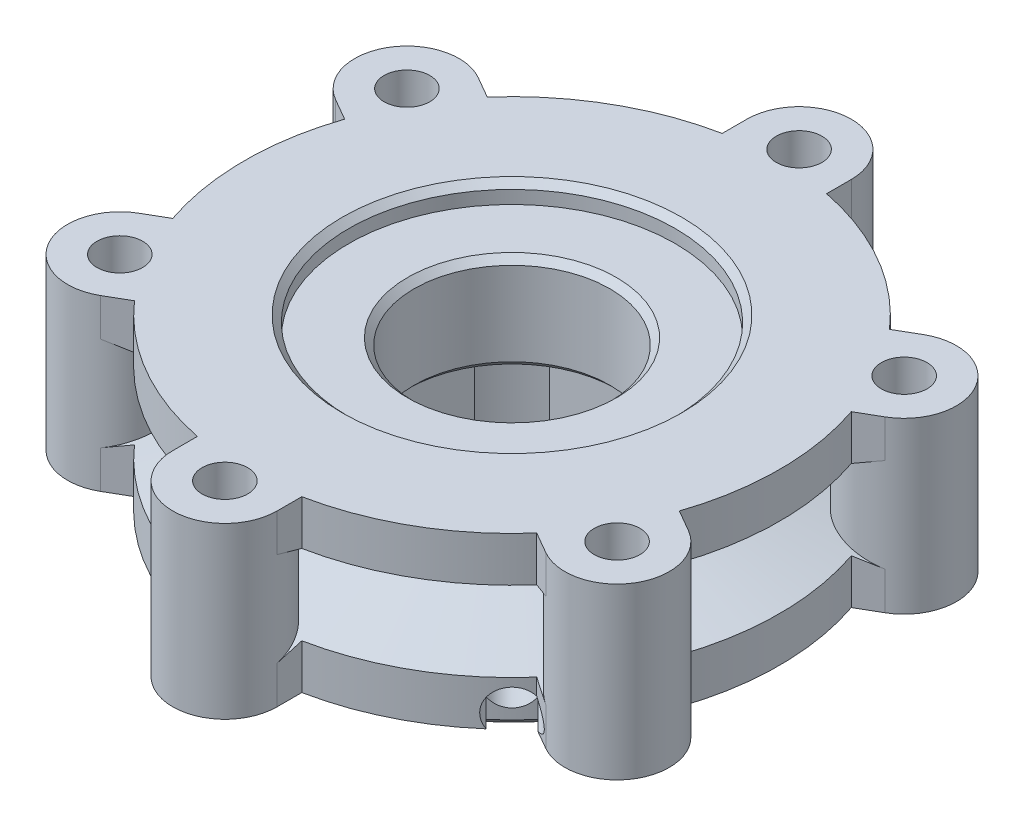
SolidWorks part; units mm, degrees
material "PLA/ABS"
ref_plane "Front Plane" through (0, 0, 0) normal (0, 0, 1) x (1, 0, 0)
ref_plane "Top Plane" through (0, 0, 0) normal (0, 1, 0) x (1, 0, 0)
ref_plane "Right Plane" through (0, 0, 0) normal (1, 0, 0) x (0, 0, -1)
other "Bounding Box"
ref_plane "Default Plane" through (13.8565, 3.175, 6.7999) normal (0, -1, 0) x (-1, 0, 0)
sketch "Sketch1" plane through (0, 0, 0) normal (0, 1, 0) x (1, 0, 0)
  line L0 (26.9408, -26.9408) -> (0, 0) construction
  line L1 (0, 0) -> (26.9408, 26.9408) construction
  line L2 (0, 0) -> (0, 38.1) construction
  circle A0 centre (0, 0) radius 38.1
  point P3 (0, 38.1)
  point P4 (38.1, 0)
  point P5 (-38.1, 0)
  point P6 (0, -38.1)
  point P7 (26.9408, 26.9408)
  point P8 (26.9408, -26.9408)
  dimension "D1" = 76.2
  dimension "D2" = 45
extrude "Boss-Extrude1" add sketch "Sketch1" along normal mid plane 16.51
ref_plane "Plane2" through (-38.1, 0, 0) normal (-1, 0, 0) x (0, 0, 1)
sketch "Sketch9" plane through (-38.1, 0, 0) normal (-1, 0, 0) x (0, 0, 1)
  line L0 (-0.635, -8.255) -> (0.635, -8.255)
  line L1 (-38.1, -8.255) -> (38.1, -8.255) construction
  line L2 (0.635, -8.255) -> (0.635, 0)
  line L3 (38.1, 8.255) -> (-38.1, 8.255) construction
  line L5 (-0.635, 0) -> (-0.635, -8.255)
  line L6 (0.635, -8.255) -> (0, -8.255) construction
  line L7 (0, -8.255) -> (0, 8.255) construction
  line L9 (-0.635, 0) -> (0.635, 0) construction
  line L10 (0.635, 0) -> (0.635, 8.255)
  line L11 (0.635, 8.255) -> (-0.635, 8.255)
  line L13 (-0.635, 8.255) -> (-0.635, 0)
  point P14 (0, 0)
  dimension "D2" = 1.27
extrude "Cut-Extrude4" cut sketch "Sketch9" against normal blind 0.635
sketch "Sketch4" plane through (0, 0, 0) normal (0, 0, 1) x (1, 0, 0)
  line L0 (-38.1, -8.255) -> (-35.56, -8.255)
  line L1 (-38.0947, -8.255) -> (38.1, -8.255) construction
  line L4 (38.1, 8.255) -> (-38.0947, 8.255) construction
  line L5 (-35.56, 8.255) -> (-38.1, 8.255)
  line L6 (-38.1, 8.255) -> (-38.1, -8.255)
  line L7 (-12.7, 0) -> (0, 0) construction
  line L8 (-35.56, -8.255) -> (-35.56, -6.6675)
  line L9 (-35.56, -6.6675) -> (-12.7, 0)
  line L10 (-12.7, 0) -> (-35.56, 6.6675)
  line L11 (-35.56, 6.6675) -> (-35.56, 8.255)
  point P17 (-38.1, 0)
  dimension "D1" = 2.54
  dimension "D2" = 25.4
  dimension "D3" = 1.5875
pattern_circular "CirPattern2" count 25 over 360 about axis through (0, -8.255, 0) along (0, 1, 0) of "Cut-Extrude4"
ref_axis "Axis1" through (0, -8.7312, 0) along (0, 1, 0)
sketch "Sketch3" plane through (0, 8.255, 0) normal (0, 1, 0) x (1, 0, 0)
  line L0 (0, 0) -> (0, 27.94) construction
  line L1 (0, 27.94) -> (0, 38.1) construction
  circle A0 centre (0, 27.94) radius 2.2225
  circle A1 centre (0, 0) radius 38.1 construction
  circle A2 centre (0, 27.94) radius 5.08
  dimension "D2" = 4.445
  dimension "D3" = 10.16
  dimension "D1" = 10.16
move or copy body "Body-Move/Copy1" [suppressed]
revolve "Cut-Revolve2" cut sketch "Sketch4" angle 360 about axis through (0, -8.7312, 0) along (0, 1, 0)
sketch "Sketch5" plane through (0, 8.255, 0) normal (0, 1, 0) x (1, 0, 0)
  circle A0 centre (0, 27.94) radius 5.08
  circle A1 centre (0, 27.94) radius 2.2225 construction
  circle A3 centre (0, 27.94) radius 2.2225
  circle A4 centre (0, 27.94) radius 5.08 construction
extrude "Boss-Extrude2" add sketch "Sketch5" against normal through all
sketch "Sketch12" plane through (0, 8.255, 0) normal (0, 1, 0) x (1, 0, 0)
  line L0 (-24.1967, 13.97) -> (0, 0) construction
  line L1 (-24.1967, -13.97) -> (-24.1967, 13.97) construction
  line L2 (-24.1967, 13.97) -> (0, 27.94) construction
  line L3 (-24.1967, -13.97) -> (0, 0) construction
  line L4 (0, 0) -> (0, 27.94) construction
  circle A0 centre (-24.1967, 13.97) radius 5.08
  circle A1 centre (0, 27.94) radius 5.08 construction
  dimension "D3" = 120
extrude "Boss-Extrude6" add sketch "Sketch12" against normal through all
sketch "Sketch17" plane through (0, 0, 0) normal (0, 1, 0) x (1, 0, 0)
  line L0 (0, 27.94) -> (0, 0) construction
  line L1 (0, 0) -> (-24.1967, 13.97) construction
  line L2 (0, 0) -> (-24.1967, -13.97) construction
  line L3 (-28.5962, -16.51) -> (-30.7959, -17.78)
  line L4 (0, 33.02) -> (0, 35.56)
  line L5 (-26.7367, -9.5706) -> (-24.6536, -8.3679)
  line L6 (-24.6536, 8.3679) -> (-26.7367, 9.5706)
  line L7 (-21.6567, 18.3694) -> (-19.5736, 17.1667)
  line L8 (-5.08, 27.94) -> (-5.08, 25.5346)
  circle A0 centre (0, 27.94) radius 5.08 construction
  circle A1 centre (-24.1967, 13.97) radius 5.08 construction
  arc A2 (0, 33.02) -> (-5.08, 27.94) centre (0, 27.94) ccw
  arc A3 (-21.6567, 18.3694) -> (-26.7367, 9.5706) centre (-24.1967, 13.97) ccw
  arc A5 (-5.08, 25.5346) -> (-19.5736, 17.1667) centre (0, 0) ccw
  circle A6 centre (0, 27.94) radius 2.2225 construction
  arc A7 (-26.7367, -9.5706) -> (-28.5962, -16.51) centre (-24.1967, -13.97) ccw
  circle A8 centre (0, 0) radius 35.56 construction
  circle A9 centre (0, 27.94) radius 2.2225
  circle A10 centre (0, 0) radius 35.56 construction
  arc A11 (0, 35.56) -> (-30.7959, -17.78) centre (0, 0) ccw
  arc A12 (-24.6536, 8.3679) -> (-24.6536, -8.3679) centre (0, 0) ccw
  circle A13 centre (-24.1967, 13.97) radius 2.2225
  circle A15 centre (-24.1967, -13.97) radius 2.2225
  dimension "D1" = 9.525
extrude "Cut-Extrude5" cut sketch "Sketch17" against normal through all both and the other way through all
pattern_circular "CirPattern1" count 3 over 360 about axis through (0, 6.6675, 0) along (0, -1, 0) of "Boss-Extrude2", "Boss-Extrude6", "Cut-Extrude5"
sketch "Sketch18" plane through (0, -8.255, 0) normal (0, -1, 0) x (1, 0, 0)
  circle A0 centre (0, 0) radius 26.035 construction
  circle A1 centre (0, 0) radius 16.51
  arc A2 (-5.08, 25.5346) -> (-19.5736, 17.1667) centre (0, 0) ccw construction
  circle A3 centre (0, 0) radius 12.7 construction
  circle A4 centre (0, 0) radius 12.7 construction
  dimension "D1" = 3.81
extrude "Boss-Extrude9" add sketch "Sketch18" against normal through all
fillet "Fillet5" radius 1.27 2 edges at (0, -1.1112, -16.51) (0, 1.1112, 16.51)
sketch "Sketch22" plane through (0, -8.255, 0) normal (0, -1, 0) x (1, 0, 0)
  circle A0 centre (0, 0) radius 22.225
  dimension "D1" = 44.45
extrude "Boss-Extrude12" add sketch "Sketch22" along normal blind 2.54
sketch "Sketch23" plane through (0, -10.795, 0) normal (0, -1, 0) x (1, 0, 0)
  line L0 (-8.5312, 8.5312) -> (-18.4095, 18.4095) construction
  line L1 (8.5312, 8.5312) -> (18.4095, 18.4095) construction
  arc A2 (24.6536, -8.3679) -> (24.6536, 8.3679) centre (0, 0) ccw construction
  arc A3 (-5.08, 25.5346) -> (-19.5736, 17.1667) centre (0, 0) ccw construction
  arc A4 (19.5736, 17.1667) -> (5.08, 25.5346) centre (0, 0) ccw construction
  line B0 (0, -10.16) -> (-6.5068, -10.16)
  line B1 (6.5068, -10.16) -> (0, -10.16)
  line B2 (10.16, 6.5068) -> (10.16, -6.5068)
  line B3 (0, 10.16) -> (6.5068, 10.16)
  line B4 (-6.5068, 10.16) -> (0, 10.16)
  line B5 (-10.16, -6.5068) -> (-10.16, 6.5068)
  arc B6 (-10.16, -6.5068) -> (-6.5068, -10.16) centre (0, 0) ccw
  arc B7 (6.5068, -10.16) -> (10.16, -6.5068) centre (0, 0) ccw
  arc B8 (10.16, 6.5068) -> (6.5068, 10.16) centre (0, 0) ccw
  arc B9 (-6.5068, 10.16) -> (-10.16, 6.5068) centre (0, 0) ccw
sketch_block_instance "Block-BaneBots Hub-1"
sketch_block "Block-BaneBots Hub"
extrude "Cut-Extrude6" cut sketch "Sketch23" against normal blind 7.747
sketch "Sketch24" plane through (0, -3.048, 0) normal (0, -1, 0) x (1, 0, 0)
  circle A0 centre (0, 0) radius 9.525
  dimension "D1" = 19.05
extrude "Cut-Extrude7" cut sketch "Sketch24" against normal through all
sketch "Sketch25" plane through (0, 8.255, 0) normal (0, 1, 0) x (1, 0, 0)
  circle A0 centre (0, 0) radius 15.875
  dimension "D1" = 31.75
extrude "Cut-Extrude8" cut sketch "Sketch25" against normal offset from surface (1.905 mm away) 17.145 up to face at (0, -10.795, 0)
ref_plane "Plane3" through (0, 0, 0) normal (0.7071, 0, -0.7071) x (-0.7071, 0, -0.7071)
sketch "Sketch33" plane through (0, 0, 0) normal (0.7071, 0, -0.7071) x (-0.7071, 0, -0.7071)
  line L0 (0, -3.048) -> (0, -10.795) construction
  line L1 (-2.5832, -10.795) -> (2.5832, -10.795) construction
  line L2 (-2.5832, -3.048) -> (2.5832, -3.048) construction
  circle A0 centre (0, -6.9215) radius 2.2225
  dimension "D1" = 4.445
extrude "Cut-Extrude9" cut sketch "Sketch33" along normal through all
ref_plane "Plane4" through (0, 0, 0) normal (0.7071, 0, 0.7071) x (0.7071, 0, -0.7071)
sketch "Sketch34" plane through (0, 0, 0) normal (0.7071, 0, 0.7071) x (0.7071, 0, -0.7071)
  line L0 (0, -3.048) -> (0, -10.795) construction
  line L1 (-2.5832, -10.795) -> (2.5832, -10.795) construction
  line L2 (-2.5832, -3.048) -> (2.5832, -3.048) construction
  circle A0 centre (0, -6.9215) radius 2.2225
  dimension "D1" = 4.445
extrude "Cut-Extrude10" cut sketch "Sketch34" along normal through all
sketch "Sketch37" plane through (0, 0, 0) normal (0.7071, 0, -0.7071) x (-0.7071, 0, -0.7071)
  circle A0 centre (0, -6.9215) radius 3.175
  circle A1 centre (0, -6.9215) radius 2.2225
  arc A2 (1.778, -8.255) -> (-1.7019, -5.4922) centre (0, -6.9215) ccw construction
  dimension "D1" = 6.35
extrude "Boss-Extrude19" [suppressed] add sketch "Sketch37" along normal up to vertex from offset 19.05 up to point (26.9408, 0, -26.9408)
sketch "Sketch39" plane through (0, 0, 0) normal (0.7071, 0, 0.7071) x (0.7071, 0, -0.7071)
  circle A0 centre (0, -6.9215) radius 3.175
  circle A1 centre (0, -6.9215) radius 2.2225
  arc A2 (1.7019, -5.4922) -> (-1.778, -8.255) centre (0, -6.9215) ccw construction
  dimension "D1" = 6.35
extrude "Boss-Extrude20" [suppressed] add sketch "Sketch39" along normal up to vertex from offset 19.05 up to point (26.9408, 0, 26.9408)
fillet "Fillet8" [suppressed] radius 0.635
chamfer "Chamfer5" distance 0.635 angle 45 12 edges at (0, -10.795, -22.225) (0, -10.795, -10.16) (8.5312, -10.795, -8.5312) (10.16, -10.795, 0) (8.5312, -10.795, 8.5312) (0, -10.795, 10.16) (-8.5312, -10.795, 8.5312) (-10.16, -10.795, 0) (-8.5312, -10.795, -8.5312) (0, 8.255, 15.875) (0, 6.35, -9.525) (0, -3.048, -9.525)
combine bodies "Combine3" [suppressed] bodies to combine 116 169
delete or keep bodies "Body-Delete/Keep 4" [suppressed] type keep bodies bodies 117
sketch "Sketch7" [suppressed] plane through (0, -8.255, 0) normal (0, -1, 0) x (1, 0, 0)
  circle A0 centre (0, 0) radius 44.45
  circle A1 centre (0, 0) radius 38.1 construction
  dimension "D1" = 6.35
extrude "Boss-Extrude4" [suppressed] add sketch "Sketch7" against normal offset from surface (19.685 mm away) 3.175 separate body up to face at (0, 8.255, 16.51) offset beyond the face yes
combine bodies "Combine2" [suppressed] operation type subtract main body 110 bodies to subtract 114
sketch "Sketch15" [suppressed] plane through (0, 0, 0) normal (1, 0, 0) x (0, 0, -1)
  line L0 (-44.45, -8.255) -> (-49.53, -13.335)
  line L1 (-49.53, -13.335) -> (-43.18, -13.335)
  line L2 (-43.18, -13.335) -> (-38.1, -8.255)
  line L3 (-38.1, -8.255) -> (-44.45, -8.255)
  dimension "D1" = 5.08
  dimension "D2" = 45
ref_axis "Axis2" [suppressed] through (0, -9.9352, 0) along (0, 1, 0)
revolve "Revolve1" [suppressed] add sketch "Sketch15" angle 360 about axis through (0, -9.9352, 0) along (0, 1, 0)
fillet "Fillet4" [suppressed] radius 6.35
sketch "Sketch27" [suppressed] plane through (0, 11.43, 0) normal (0, 1, 0) x (1, 0, 0)
  line L0 (43.9941, 6.35) -> (50.8, 6.35)
  line L1 (50.8, -6.35) -> (43.9941, -6.35)
  line L2 (44.45, 0) -> (50.8, 0) construction
  circle A0 centre (50.8, 0) radius 1.905
  arc A1 (43.9941, -6.35) -> (43.9941, 6.35) centre (0, 0) ccw
  circle A2 centre (0, 0) radius 44.45 construction
  arc A3 (50.8, 6.35) -> (50.8, -6.35) centre (50.8, 0) cw
  dimension "D2" = 3.81
  dimension "D3" = 6.35
  dimension "D1" = 6.35
extrude "Boss-Extrude13" [suppressed] add sketch "Sketch27" against normal blind 9.525
pattern_circular "CirPattern7" [suppressed] count 3 over 360 of bodies 177
split "Split1" [suppressed] bodies to split 178
sketch "Sketch19" [suppressed] plane through (0, 11.43, 0) normal (0, 1, 0) x (1, 0, 0)
  line L0 (-43.6478, 18.0795) -> (-41.3011, 17.1075)
  line L1 (-43.6478, -18.0795) -> (-41.3011, -17.1075)
  line L2 (-47.244, 0) -> (0, 0) construction
  arc A0 (-41.3011, 17.1075) -> (-41.3011, -17.1075) centre (0, 0) ccw
  circle A1 centre (0, 0) radius 44.45 construction
  arc A2 (-43.6478, 18.0795) -> (-43.6478, -18.0795) centre (0, 0) ccw
  dimension "D2" = 2.54
  dimension "D3" = 0.254
  dimension "D1" = 45
extrude "Boss-Extrude10" [suppressed] add sketch "Sketch19" against normal blind 6.35 separate body
sketch "Sketch21" [suppressed] plane through (0, 11.43, 0) normal (0, 1, 0) x (1, 0, 0)
  line L0 (-41.3011, 17.1075) -> (-41.0664, 17.0103)
  line L1 (-41.3011, -17.1075) -> (-41.0664, -17.0103)
  line L2 (-41.3011, 17.1075) -> (-43.6478, 18.0795) construction
  line L3 (-43.6478, -18.0795) -> (-41.3011, -17.1075) construction
  arc A1 (-41.3011, 17.1075) -> (-41.3011, -17.1075) centre (0, 0) ccw construction
  arc A2 (-41.0664, 17.0103) -> (-41.0664, -17.0103) centre (0, 0) ccw
  arc A3 (-41.3011, 17.1075) -> (-41.3011, -17.1075) centre (0, 0) ccw
  circle A4 centre (0, 0) radius 44.45 construction
extrude "Boss-Extrude11" [suppressed] add sketch "Sketch21" against normal blind 3.1496
pattern_circular "CirPattern6" [suppressed] count 3 over 360 reverse direction yes of bodies 137 132
combine bodies "Combine4" [suppressed] bodies to combine 137 137 135 134
chamfer "Chamfer4" [suppressed] distance 0.635 angle 45
delete or keep bodies "Body-Delete/Keep 1" [suppressed] type delete bodies bodies 133
delete or keep bodies "Body-Delete/Keep 2" [suppressed] type delete bodies bodies 121
mirror "Mirror1" [suppressed] about plane through (0, 0, 0) normal (1, 0, 0) of bodies 121
delete or keep bodies "Body-Delete/Keep 3" [suppressed] type delete bodies bodies 121
sketch "Sketch28" [suppressed] plane through (0, 8.255, 0) normal (0, -1, 0) x (1, 0, 0)
  circle A0 centre (0, 0) radius 15.24
  dimension "D1" = 30.48
extrude "Boss-Extrude14" [suppressed] add sketch "Sketch28" along normal blind 1.27
sketch "Sketch29" [suppressed] plane through (0, 6.985, 0) normal (0, -1, 0) x (1, 0, 0)
  circle A0 centre (0, 0) radius 9.398
  dimension "D1" = 18.796
extrude "Boss-Extrude15" [suppressed] add sketch "Sketch29" along normal blind 10.16
sketch "Sketch30" [suppressed] plane through (0, -8.255, 0) normal (0, -1, 0) x (1, 0, 0)
  circle A12 centre (0, 0) radius 36.83
  circle A13 centre (0, 0) radius 34.29
  circle A14 centre (0, 0) radius 38.1 construction
  dimension "D1" = 1.27
  dimension "D2" = 2.54
extrude "Boss-Extrude16" [suppressed] add sketch "Sketch30" along normal blind 1.6002 separate body
sketch "Sketch31" [suppressed] plane through (0, -9.8552, 0) normal (0, -1, 0) x (1, 0, 0)
  line L0 (-4.1275, 27.94) -> (-4.1275, 36.598)
  line L1 (-4.1275, 36.598) -> (4.1275, 36.598)
  line L2 (4.1275, 36.598) -> (4.1275, 27.94)
  circle A0 centre (0, 27.94) radius 2.2225 construction
  circle A1 centre (0, 27.94) radius 2.2225
  arc A2 (4.1275, 27.94) -> (-4.1275, 27.94) centre (0, 27.94) cw
  circle A4 centre (0, 0) radius 36.83 construction
  dimension "D1" = 1.905
extrude "Boss-Extrude17" [suppressed] add sketch "Sketch31" against normal up to surface (1.6002 mm away) up to face at (22.272, -8.255, -15.0812)
fillet "Fillet6" [suppressed] radius 2.54
pattern_circular "CirPattern8" [suppressed] count 6 over 360 of bodies 182
sketch "Sketch32" [suppressed] plane through (0, -9.8552, 0) normal (0, -1, 0) x (1, 0, 0)
  line L0 (0, 0) -> (-2.7463, 39.2741) construction
  line L1 (2.7463, 39.2741) -> (0.7608, 36.8221)
  line L2 (0, 0) -> (0, 39.37) construction
  line L3 (-2.3026, 36.7579) -> (-2.7463, 39.2741)
  line L4 (-2.7463, 39.2741) -> (-0.7608, 36.8221)
  line L5 (-0.7608, 36.8221) -> (-2.3026, 36.7579)
  line L6 (2.3026, 36.7579) -> (2.7463, 39.2741)
  line L7 (0.7608, 36.8221) -> (2.3026, 36.7579)
  circle A0 centre (0, 0) radius 36.83 construction
  circle A1 centre (0, 0) radius 39.37 construction
  circle A2 centre (0, 0) radius 38.1 construction
  dimension "D2" = 1.27
  dimension "D1" = 6
  dimension "D3" = 35
  dimension "D4" = 4
extrude "Boss-Extrude18" [suppressed] add sketch "Sketch32" against normal up to surface (1.6002 mm away) up to face at (22.272, -8.255, -15.0812)
fillet "Fillet7" [suppressed] radius 0.635
pattern_circular "CirPattern9" [suppressed] count 10 over 360 of bodies 184
delete or keep bodies "Body-Delete/Keep 5" [suppressed] bodies 185
